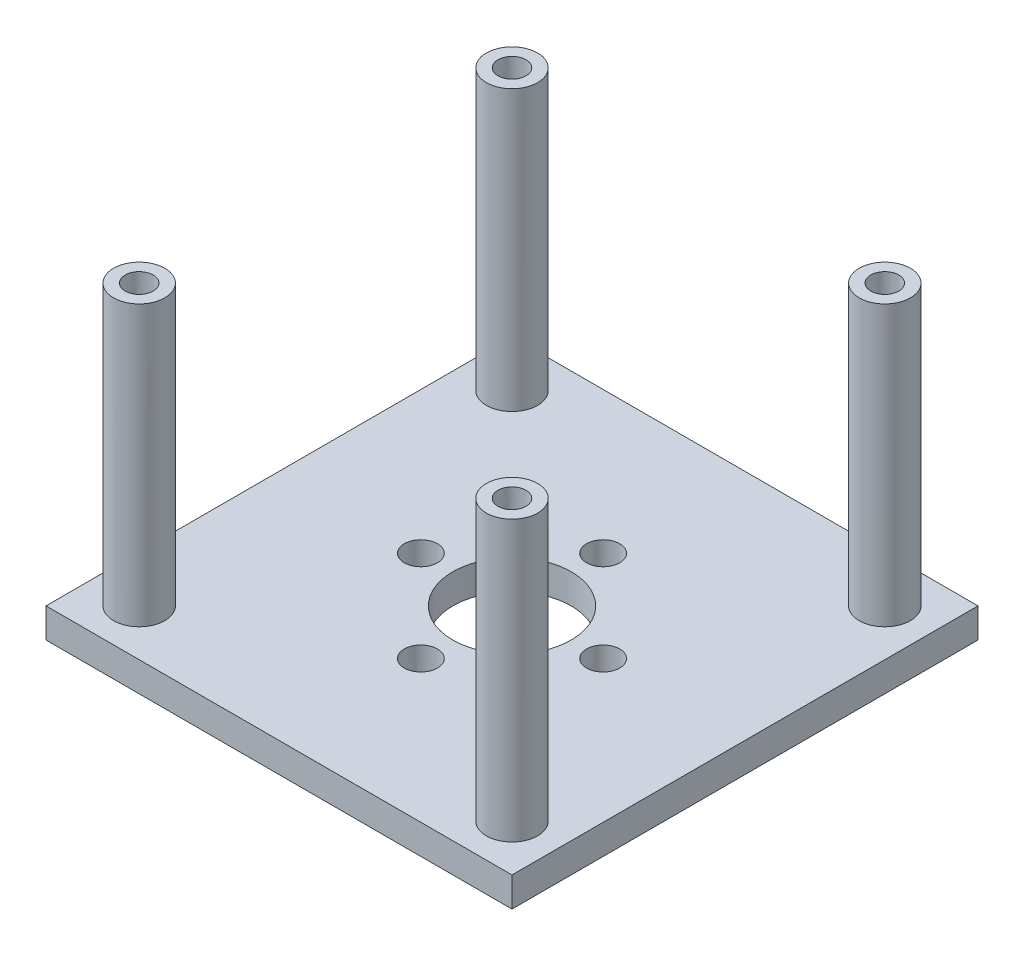
SolidWorks part; units mm, degrees
material "Copper"
ref_plane "Front Plane" through (0, 0, 0) normal (0, 0, 1) x (1, 0, 0)
ref_plane "Top Plane" through (0, 0, 0) normal (0, 1, 0) x (1, 0, 0)
ref_plane "Right Plane" through (0, 0, 0) normal (1, 0, 0) x (0, 0, -1)
sketch "Sketch1" plane through (0, 0, 0) normal (0, 1, 0) x (1, 0, 0)
  line L1 (-25, -25) -> (25, -25)
  line L2 (-25, -25) -> (-25, 25)
  line L3 (-25, 25) -> (25, 25)
  line L4 (25, -25) -> (25, 25)
  line L5 (-25, -25) -> (25, 25) construction
  line L6 (-25, 25) -> (25, -25) construction
  circle A0 centre (0, 0) radius 6.35
  circle A1 centre (-9.779, 0) radius 1.778
  circle A2 centre (9.779, 0) radius 1.778
  circle A3 centre (0, 9.779) radius 1.778
  circle A4 centre (0, -9.779) radius 1.778
  point P0 (0, 0)
  point P16 (0, 0)
  point P17 (0, 0)
  point P18 (0, 0)
  dimension "D3" = 12.7
  dimension "D8" = 3.556
  dimension "D9" = 3.556
  dimension "D10" = 3.556
  dimension "D11" = 3.556
  dimension "D1" = 50
  dimension "D2" = 50
  dimension "D4" = 9.779
  dimension "D5" = 9.779
  dimension "D6" = 9.779
  dimension "D7" = 9.779
extrude "Boss-Extrude1" add sketch "Sketch1" along normal blind 3.175
sketch "Sketch2" plane through (0, 3.175, 0) normal (0, 1, 0) x (1, 0, 0)
  line L0 (25, 25) -> (-25, 25) construction
  line L1 (-25, 25) -> (-25, -25) construction
  line L2 (25, -25) -> (25, 25) construction
  line L3 (-25, -25) -> (25, -25) construction
  circle A0 centre (20, -20) radius 2.75
  circle A1 centre (-20, -20) radius 2.75
  circle A2 centre (-20, 20) radius 2.75
  circle A3 centre (20, 20) radius 2.75
  circle A4 centre (-20, -20) radius 1.5
  circle A5 centre (20, -20) radius 1.5
  circle A6 centre (-20, 20) radius 1.5
  circle A7 centre (20, 20) radius 1.5
  point P16 (0, 0)
  point P18 (-34.6882, 6.2346)
  dimension "D1" = 5
  dimension "D9" = 3
  dimension "D10" = 5.5
  dimension "D11" = 3
  dimension "D12" = 5.5
  dimension "D13" = 3
  dimension "D14" = 5.5
  dimension "D15" = 3
  dimension "D16" = 5.5
  dimension "D2" = 5
  dimension "D3" = 5
  dimension "D4" = 5
  dimension "D5" = 5
  dimension "D6" = 5
  dimension "D7" = 5
  dimension "D8" = 5
extrude "Boss-Extrude2" add sketch "Sketch2" along normal blind 30
